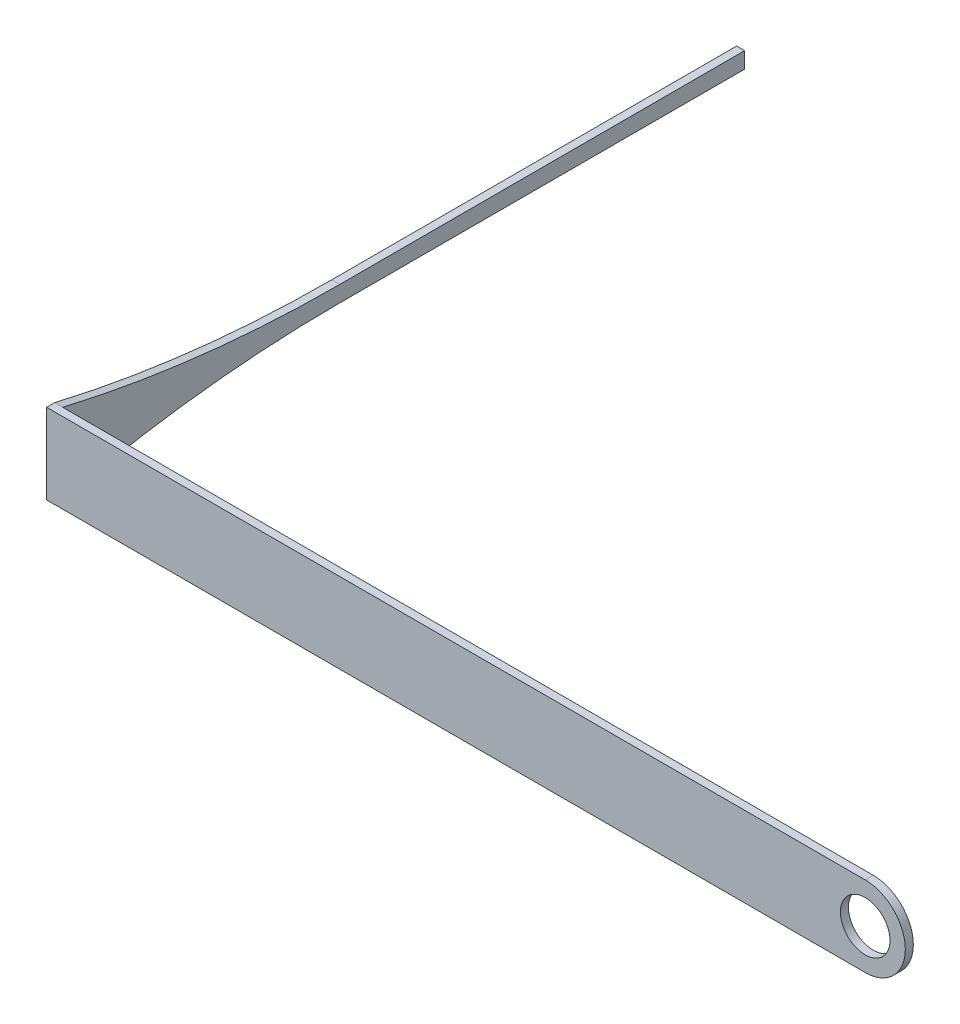
SolidWorks part; units mm, degrees
ref_plane "Front Plane" through (0, 0, 0) normal (0, 0, 1) x (1, 0, 0)
ref_plane "Top Plane" through (0, 0, 0) normal (0, 1, 0) x (1, 0, 0)
ref_plane "Right Plane" through (0, 0, 0) normal (1, 0, 0) x (0, 0, -1)
sketch "Sketch1" plane through (0, 0, 0) normal (0, 1, 0) x (1, 0, 0)
  line L0 (0, 0) -> (-101, 0)
  line L1 (-101, 0) -> (-101, 84.9819)
  line L2 (0, -1) -> (-102, -1)
  line L3 (-102, -1) -> (-102, 84.9819)
  line L4 (0, 0) -> (0, -1)
  line L5 (-102, 84.9819) -> (-101, 84.9819)
  dimension "D2" = 101
  dimension "D1" = 1
extrude "Boss-Extrude1" add sketch "Sketch1" along normal mid plane 10
sketch "Sketch2" plane through (0, 0, 1) normal (0, 0, 1) x (1, 0, 0)
  line L0 (-102, 5) -> (0, 5) construction
  circle A0 centre (0, 0) radius 3.0889
  circle A1 centre (0, 0) radius 5
extrude "Boss-Extrude2" add sketch "Sketch2" against normal up to surface (1 mm away) contours A1 A0 region at (-4.8586, 0, 1) up to face at (-50.5, 0, 0)
sketch "Sketch3" plane through (0, 0, 1) normal (0, 0, 1) x (1, 0, 0)
  circle A0 centre (0, 0) radius 3.0889
  arc A1 (0, -3.0889) -> (0, 3.0889) centre (0, 0) ccw construction
extrude "Cut-Extrude1" cut sketch "Sketch3" against normal up to surface (1 mm away) up to face at (-49.25, 0, 0)
ref_axis "Axis1" through (0, 0, 0) along (0, 0, 1)
sketch "Sketch4" plane through (-102, 0, 0) normal (-1, 0, 0) x (0, 0, 1)
  line L0 (-84.9819, -1) -> (-84.9819, 1)
  line L1 (-84.9819, 5) -> (-84.9819, -5) construction
  line L2 (-84.9819, 1) -> (-34.5274, 1)
  line L3 (-84.9819, -1) -> (-34.5274, -1)
  line L4 (-84.9819, 0) -> (-74.9325, 0) construction
  arc A0 (-34.5274, 1) -> (0, 5) centre (-34.5274, 152.0179) ccw
  arc A1 (-34.5274, -1) -> (0, -5) centre (-34.5274, -152.0179) cw
  point P5 (-84.9819, 0)
  line M7 (-84.9819, -5) -> (1, -5)
  line M9 (1, 5) -> (-84.9819, 5)
  line M10 (-84.9819, 5) -> (-84.9819, -5)
  dimension "D1" = 2
extrude "Cut-Extrude2" cut sketch "Sketch4" against normal blind 10 and the other way through all contours L2 A0 M9 M10 | A1 L3 M10 M7 region at (-102, 3.125, -47.7656) region at (-102, -3.125, -47.7656)
